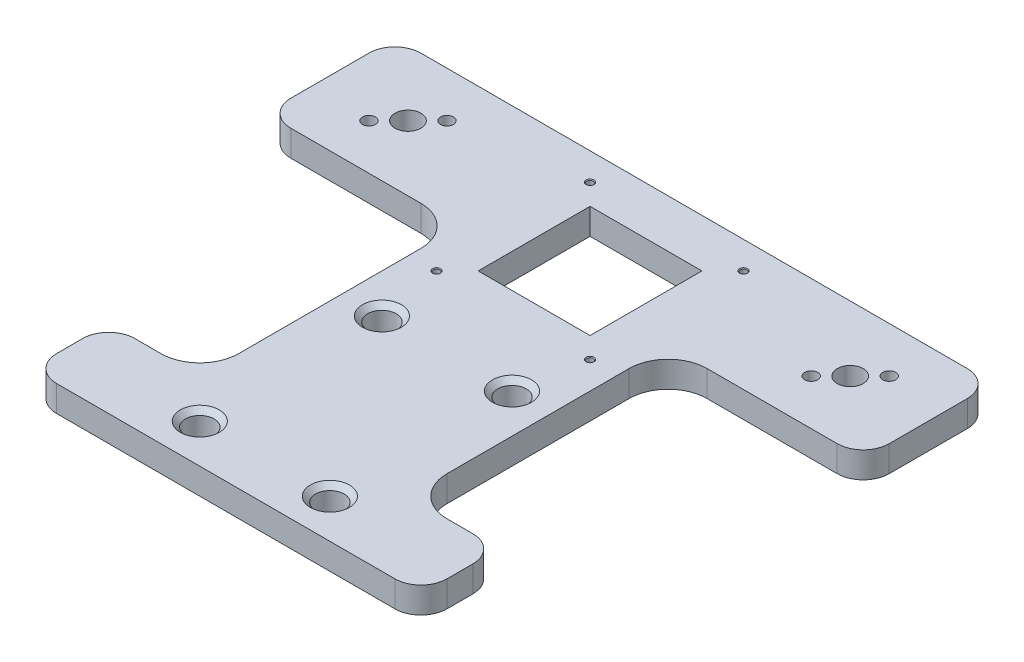
SolidWorks part; units mm, degrees
ref_plane "Vorne" through (0, 0, 0) normal (0, 0, 1) x (1, 0, 0)
ref_plane "Oben" through (0, 0, 0) normal (0, 1, 0) x (1, 0, 0)
ref_plane "Rechts" through (0, 0, 0) normal (1, 0, 0) x (0, 0, -1)
ref_plane "E_Boden" through (0, 1, 0) normal (0, 1, 0) x (1, 0, 0)
sketch "Skizze1" plane through (0, 0, 0) normal (0, 1, 0) x (1, 0, 0)
  line L0 (0, -84.2382) -> (0, 127.1868) construction
  line L1 (-165.4867, 0) -> (188.3198, 0) construction
  line L2 (-105, 90) -> (105, 90)
  line L3 (-115, 80) -> (-115, 50)
  line L8 (-105, 40) -> (-55, 40)
  line L9 (-40, 25) -> (-40, -45)
  line L10 (-55, -60) -> (-65, -60)
  line L11 (-75, -70) -> (-75, -80)
  line L12 (-65, -90) -> (65, -90)
  line L13 (75, -70) -> (75, -80)
  line L14 (55, -60) -> (65, -60)
  line L15 (40, 25) -> (40, -45)
  line L16 (105, 40) -> (55, 40)
  line L17 (115, 80) -> (115, 50)
  arc A0 (40, 25) -> (55, 40) centre (55, 25) cw
  arc A1 (55, -60) -> (40, -45) centre (55, -45) cw
  arc A2 (-40, -45) -> (-55, -60) centre (-55, -45) cw
  arc A3 (-55, 40) -> (-40, 25) centre (-55, 25) cw
  arc A4 (75, -70) -> (65, -60) centre (65, -70) ccw
  arc A5 (75, -80) -> (65, -90) centre (65, -80) cw
  arc A6 (-75, -80) -> (-65, -90) centre (-65, -80) ccw
  arc A7 (-65, -60) -> (-75, -70) centre (-65, -70) ccw
  arc A8 (-115, 50) -> (-105, 40) centre (-105, 50) ccw
  arc A9 (105, 40) -> (115, 50) centre (105, 50) ccw
  arc A10 (115, 80) -> (105, 90) centre (105, 80) ccw
  arc A11 (-105, 90) -> (-115, 80) centre (-105, 80) ccw
  point P15 (0, -90)
  point P16 (0, 90)
  point P22 (40, 40)
  point P25 (40, -60)
  point P28 (-40, -60)
  point P31 (-40, 40)
  point P34 (75, -60)
  point P37 (75, -90)
  point P40 (-75, -90)
  point P43 (-75, -60)
  point P46 (-115, 40)
  point P49 (115, 40)
  point P52 (115, 90)
  point P55 (-115, 90)
  dimension "D7" = 15
  dimension "D8" = 10
  dimension "D1" = 230
  dimension "D2" = 50
  dimension "D3" = 130
  dimension "D4" = 150
  dimension "D5" = 80
  dimension "D6" = 30
extrude "Aufsatz-Linear austragen1" add sketch "Skizze1" along normal blind 10
hole_wizard "Ø10.0 (10) Durchmesser Bohrung1" positions "Skizze6" profile "Skizze7" hole size "Ø10.0" standard "DIN" end condition through all
sketch "Skizze6" plane through (0, 10, 0) normal (0, 1, 0) x (1, 0, 0)
  line L2 (105, 90) -> (-105, 90) construction
  line L3 (0, 90) -> (0, -90) construction
  line L4 (-65, -90) -> (65, -90) construction
  point P0 (-85, 65)
  point P2 (85, 65)
  dimension "D1" = 25
  dimension "D2" = 25
  dimension "D3" = 170
sketch "Skizze7" plane through (-85, 10, -65) normal (1, 0, 0) x (0, 0, 1)
  line L0 (0, 0) -> (0, 10)
  line L1 (0, 10) -> (5, 10)
  line L2 (5, 10) -> (5, 0)
  line L5 (5, 0) -> (0, 0)
  line L11 (0, -6.35) -> (0, 107.95) construction
  dimension "Bohrerdurchmesser" = 10
  dimension "Bohrungstiefe" = 10
sketch "Skizze8" plane through (0, 10, 0) normal (0, 1, 0) x (1, 0, 0)
  line L0 (0, 90) -> (0, -90) construction
  line L1 (-39.1455, 50) -> (35.4895, 50) construction
  line L3 (105, 90) -> (-105, 90) construction
  line L4 (-21.5, 71.5) -> (21.5, 71.5)
  line L5 (-21.5, 71.5) -> (-21.5, 28.5)
  line L6 (-21.5, 28.5) -> (21.5, 28.5)
  line L7 (21.5, 71.5) -> (21.5, 28.5)
  line L8 (-65, -90) -> (65, -90) construction
  dimension "D1" = 43
  dimension "D2" = 43
  dimension "D3" = 40
extrude "Schnitt-Linear austragen2" cut sketch "Skizze8" against normal blind 10
hole_wizard "M3 Gewindebohrung1" positions "Skizze9" profile "Skizze10" tap size "M3" standard "DIN"
sketch "Skizze9" plane through (0, 10, 0) normal (0, 1, 0) x (1, 0, 0)
  line L0 (0, 71.5) -> (0, 28.5) construction
  line L1 (21.5, 71.5) -> (-21.5, 71.5) construction
  line L2 (-21.5, 28.5) -> (21.5, 28.5) construction
  line L4 (-21.5, 50) -> (21.5, 50) construction
  line L5 (-21.5, 71.5) -> (-21.5, 28.5) construction
  line L6 (21.5, 28.5) -> (21.5, 71.5) construction
  point P0 (-29.5, 79.5)
  point P2 (-29.5, 20.5)
  point P4 (29.5, 20.5)
  point P6 (29.5, 79.5)
  dimension "D1" = 8
  dimension "D2" = 8
sketch "Skizze10" plane through (-29.5, 10, -79.5) normal (1, 0, 0) x (0, 0, 1)
  line L0 (0, 0) -> (0, 8.7511)
  line L1 (0, 8.7511) -> (1.25, 8)
  line L2 (1.25, 8) -> (1.25, 0.275)
  line L3 (1.25, 0.275) -> (1.525, 0)
  line L5 (1.525, 0) -> (0, 0)
  line L6 (-1.25, 0.275) -> (-1.525, 0) construction
  line L10 (0, 8.7511) -> (-1.25, 8) construction
  line L11 (0, -6.35) -> (0, 107.95) construction
  dimension "Bohrerdurchmesser" = 2.5
  dimension "Bohrungstiefe" = 8
  dimension "Senkdurchmesser (Oben)" = 3.05
  dimension "Senkwinkel (Oben)" = 90
  dimension "Spitzenwinkel" = 118
cosmetic thread "Bohrungsgewinde1" parameters "D1"=6, "D2"=3
cosmetic thread "Bohrungsgewinde2" parameters "D1"=6, "D2"=3
cosmetic thread "Bohrungsgewinde3" parameters "D1"=6, "D2"=3
cosmetic thread "Bohrungsgewinde4" parameters "D1"=6, "D2"=3
hole_wizard "Ø5.0 (5) Durchmesser Bohrung1" positions "Skizze11" profile "Skizze12" hole size "Ø5.0" standard "DIN" end condition through all
sketch "Skizze11" plane through (0, 0, 0) normal (0, -1, 0) x (-1, 0, 0)
  line L0 (77.5, 72.5) -> (77.5, 45.1453) construction
  line L3 (92.5, 57.5) -> (92.5, 79.091) construction
  line L6 (-92.5, 72.5) -> (-92.5, 57.5) construction
  line L9 (-77.5, 57.5) -> (-77.5, 72.5) construction
  line L12 (-77.5, 57.5) -> (-92.5, 57.5) construction
  line L15 (-77.5, 72.5) -> (-92.5, 72.5) construction
  line L18 (77.5, 72.5) -> (92.5, 72.5) construction
  line L21 (92.5, 57.5) -> (77.5, 57.5) construction
  line L24 (80, 65) -> (71.5087, 65) construction
  line L25 (71.5087, 65) -> (96.6058, 65) construction
  line L28 (85, 60) -> (85, 53.6887) construction
  line L29 (85, 53.6887) -> (85, 75.0654) construction
  line L30 (-90, 65) -> (-74.1442, 65) construction
  line L32 (-85, 70) -> (-85, 55.7381) construction
  circle A0 centre (85, 65) radius 5 construction
  circle A1 centre (-85, 65) radius 5 construction
  point P0 (77.5, 72.5)
  point P2 (92.5, 57.5)
  point P4 (-92.5, 72.5)
  point P6 (-77.5, 57.5)
  point P43 (85, 72.5)
  dimension "D1" = 15
  dimension "D2" = 15
  dimension "D3" = 7.5
  dimension "D4" = 7.5
  dimension "D5" = 15
  dimension "D6" = 15
  dimension "D7" = 7.5
  dimension "D8" = 7.5
sketch "Skizze12" plane through (-77.5, 0, -72.5) normal (1, 0, 0) x (0, 0, -1)
  line L0 (0, 0) -> (0, 10)
  line L1 (0, 10) -> (2.5, 10)
  line L2 (2.5, 10) -> (2.5, 0)
  line L5 (2.5, 0) -> (0, 0)
  line L11 (0, -6.35) -> (0, 107.95) construction
  dimension "Bohrerdurchmesser" = 5
  dimension "Bohrungstiefe" = 10
hole_wizard "Durchgangsloch für M101" positions "Skizze13" profile "Skizze14" hole size "M10" standard "DIN" end condition through all
sketch "Skizze13" plane through (0, 0, 0) normal (0, -1, 0) x (-1, 0, 0)
  line L0 (0, 90) -> (0, -90) construction
  line L1 (-105, 90) -> (105, 90) construction
  line L2 (65, -90) -> (-65, -90) construction
  line L4 (-40, -45) -> (-40, 25) construction
  line L5 (40, 25) -> (40, -45) construction
  point P0 (-25, -5)
  point P2 (-25, -75)
  point P4 (25, -5)
  point P6 (25, -75)
  dimension "D1" = 70
  dimension "D2" = 70
  dimension "D3" = 15
  dimension "D4" = 15
  dimension "D5" = 15
  dimension "D6" = 15
sketch "Skizze14" plane through (25, 0, 5) normal (1, 0, 0) x (0, 0, -1)
  line L0 (0, 0) -> (0, 10)
  line L1 (0, 10) -> (7.5, 10)
  line L2 (5.5, 8) -> (5.5, 0)
  line L5 (5.5, 0) -> (0, 0)
  line L7 (7.5, 10) -> (5.5, 8)
  line L8 (-7.5, 10) -> (-5.5, 8) construction
  line L11 (0, -6.35) -> (0, 107.95) construction
  dimension "Bohrerdurchmesser" = 11
  dimension "Bohrungstiefe" = 10
  dimension "Senkdurchmesser2 (Unten)" = 15
  dimension "Senkwinkel2 (Unten)" = 90
